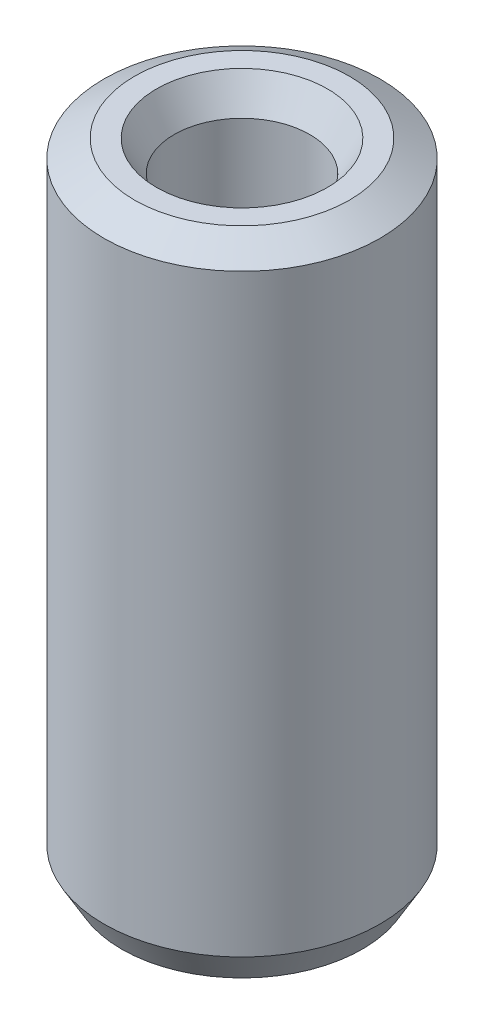
SolidWorks part; units mm, degrees
ref_plane "Front Plane" through (0, 0, 0) normal (0, 0, 1) x (1, 0, 0)
ref_plane "Top Plane" through (0, 0, 0) normal (0, 1, 0) x (1, 0, 0)
ref_plane "Right Plane" through (0, 0, 0) normal (1, 0, 0) x (0, 0, -1)
sketch "Sketch1" plane through (0, 0, 0) normal (0, 1, 0) x (1, 0, 0)
  circle A0 centre (0, 0) radius 30
  dimension "SLEEVE_OD" = 60
extrude "Boss-Extrude1" add sketch "Sketch1" along normal blind 139.5439
sketch "Sketch2" plane through (0, 0, 0) normal (0, 1, 0) x (1, 0, 0)
  circle A0 centre (0, 0) radius 14.7252
  dimension "BORE_D" = 29.4504
extrude "Cut-Extrude1" cut sketch "Sketch2" along normal through all
chamfer "Chamfer1" distance 3.8471 angle 60 4 edges at (0, 139.5439, 14.7252) (0, 0, 14.7252) (0, 0, 30) (0, 139.5439, 30) first distance on face at (0, 139.5439, 14.7252) first distance on face at (0, 0, 14.7252) first distance on face at (0, 139.5439, 30)
